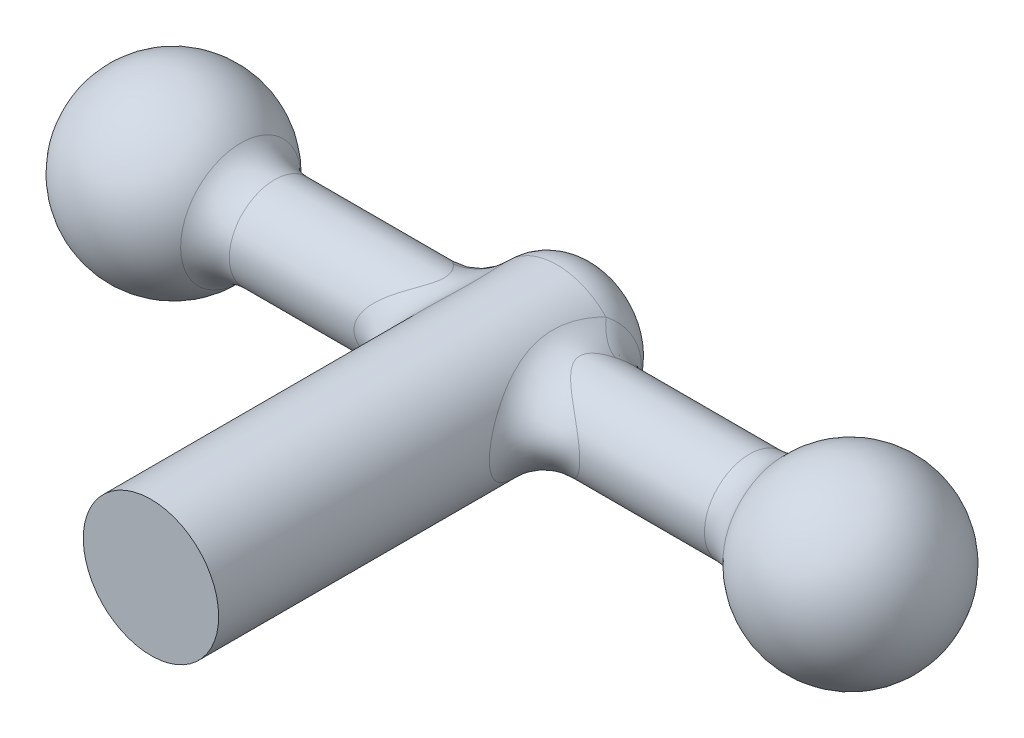
SolidWorks part; units mm, degrees
material "ABS"
ref_plane "Front Plane" through (0, 0, 0) normal (0, 0, 1) x (1, 0, 0)
ref_plane "Top Plane" through (0, 0, 0) normal (0, 1, 0) x (1, 0, 0)
ref_plane "Right Plane" through (0, 0, 0) normal (1, 0, 0) x (0, 0, -1)
sketch "Sketch1" plane through (0, 0, 0) normal (0, 0, 1) x (1, 0, 0)
  line L0 (0, 0) -> (0, 30) construction
  circle A0 centre (0, 0) radius 3
extrude "Boss-Extrude1" add sketch "Sketch1" along normal blind 20
sketch "Sketch2" plane through (0, 0, 0) normal (0, 1, 0) x (1, 0, 0)
  line L0 (0, 0) -> (0, -4) construction
  line L1 (0, -4) -> (15, -4)
ref_plane "Plane1" through (15, 0, 4) normal (1, 0, 0) x (0, 0, -1)
sketch "Sketch3" plane through (15, 0, 4) normal (1, 0, 0) x (0, 0, -1)
  line L0 (4, 0) -> (0, 0) construction
  circle A0 centre (0, 0) radius 2
extrude "Boss-Extrude3" add sketch "Sketch3" against normal blind 30
sketch "Sketch4" plane through (0, 0, 0) normal (0, 1, 0) x (1, 0, 0)
  line L0 (-15, -6) -> (-15, -2) construction
  line L1 (0, 0) -> (0, -4) construction
  line L2 (-15, 0) -> (-15, -8)
  arc A0 (-15, 0) -> (-15, -8) centre (-15, -4) ccw
revolve "Revolve1" add sketch "Sketch4" angle 360 about L2
sketch "Sketch5" plane through (0, 0, 0) normal (0, 1, 0) x (1, 0, 0)
  line L0 (15, -8) -> (15, 0)
  arc A0 (15, -8) -> (15, 0) centre (15, -4) ccw
revolve "Revolve2" add sketch "Sketch5" angle 360 about L0
fillet "Fillet1" radius 2 1 edges at (3, 0, 0)
fillet "Fillet2" radius 2 2 edges at (2.9875, 0.2736, 5.9812) (-3, 0, 6)
fillet "Fillet3" radius 2 2 edges at (11.5359, 0, 2) (-11.5359, 0, 6)
